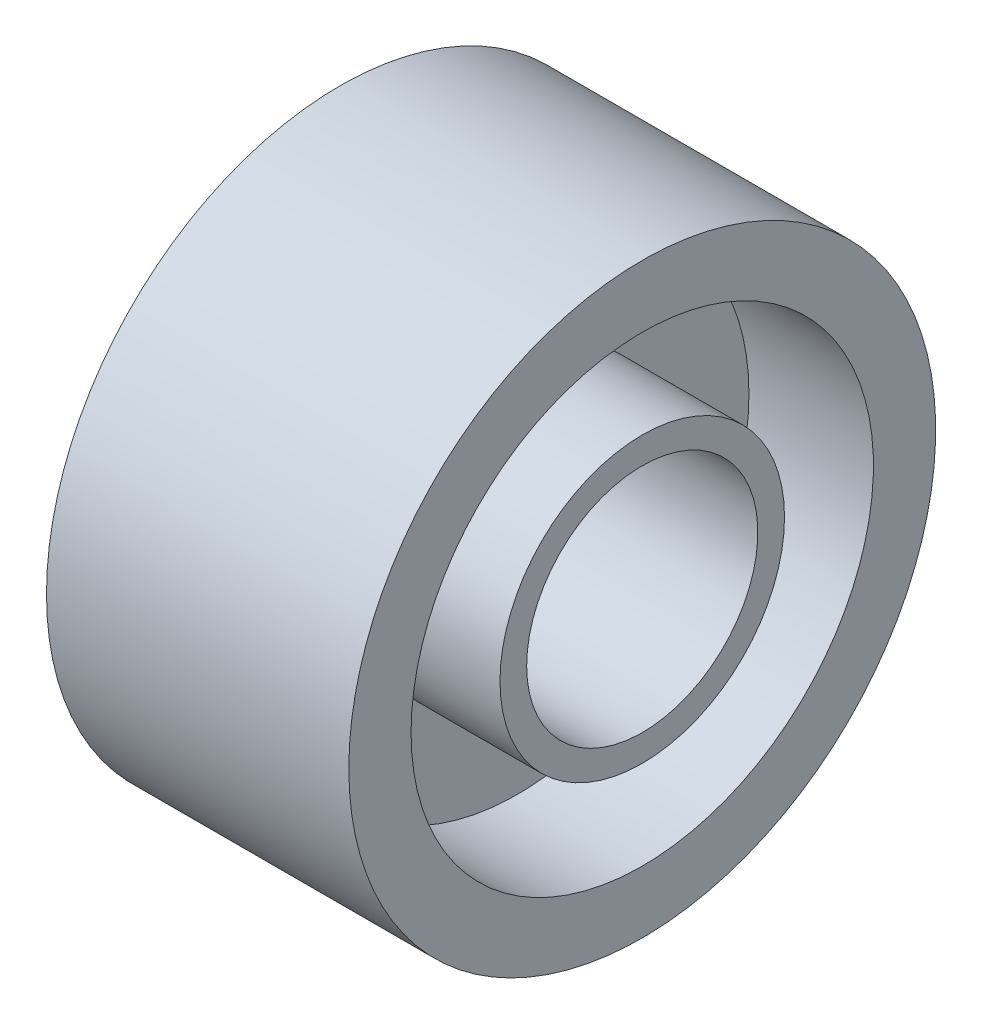
SolidWorks part; units mm, degrees
ref_plane "Alzado" through (0, 0, 0) normal (0, 0, 1) x (1, 0, 0)
ref_plane "Planta" through (0, 0, 0) normal (0, 1, 0) x (1, 0, 0)
ref_plane "Vista lateral" through (0, 0, 0) normal (1, 0, 0) x (0, 0, -1)
sketch "Croquis2" plane through (0, 0, 0) normal (1, 0, 0) x (0, 0, -1)
  circle A0 centre (0, 0) radius 16.5
  circle A1 centre (0, 0) radius 7
  circle A2 centre (0, 0) radius 8
  circle A3 centre (0, 0) radius 14
extrude "Saliente-Extruir1" add sketch "Croquis2" along normal blind 1.5 and the other way blind 1.5 contours A3 A2 | A2 A1 | A0 A3 | A1 region at (0, 0, 16.0333) region at (0, 0, 7.7737) region at (0, 0, 13.604)
sketch "Croquis3" plane through (-1.5, 0, 0) normal (-1, 0, 0) x (0, 0, 1)
  circle A0 centre (0, 0) radius 6.5
  circle A1 centre (0, 0) radius 8
  circle A2 centre (0, 0) radius 16.5
  circle A3 centre (0, 0) radius 13
  circle M1 centre (0, 0) radius 16.5
extrude "Saliente-Extruir2" add sketch "Croquis3" along normal blind 7 and the other way blind 10 contours A1 A0 | A3 M1 region at (-1.5, 0, -7.7737) region at (-1.5, 0, -16.0333)
sketch "Croquis4" plane through (-1.5, 0, 0) normal (-1, 0, 0) x (0, 0, 1)
  circle A0 centre (0, 0) radius 6.5
extrude "Cortar-Extruir1" cut sketch "Croquis4" against normal blind 7
